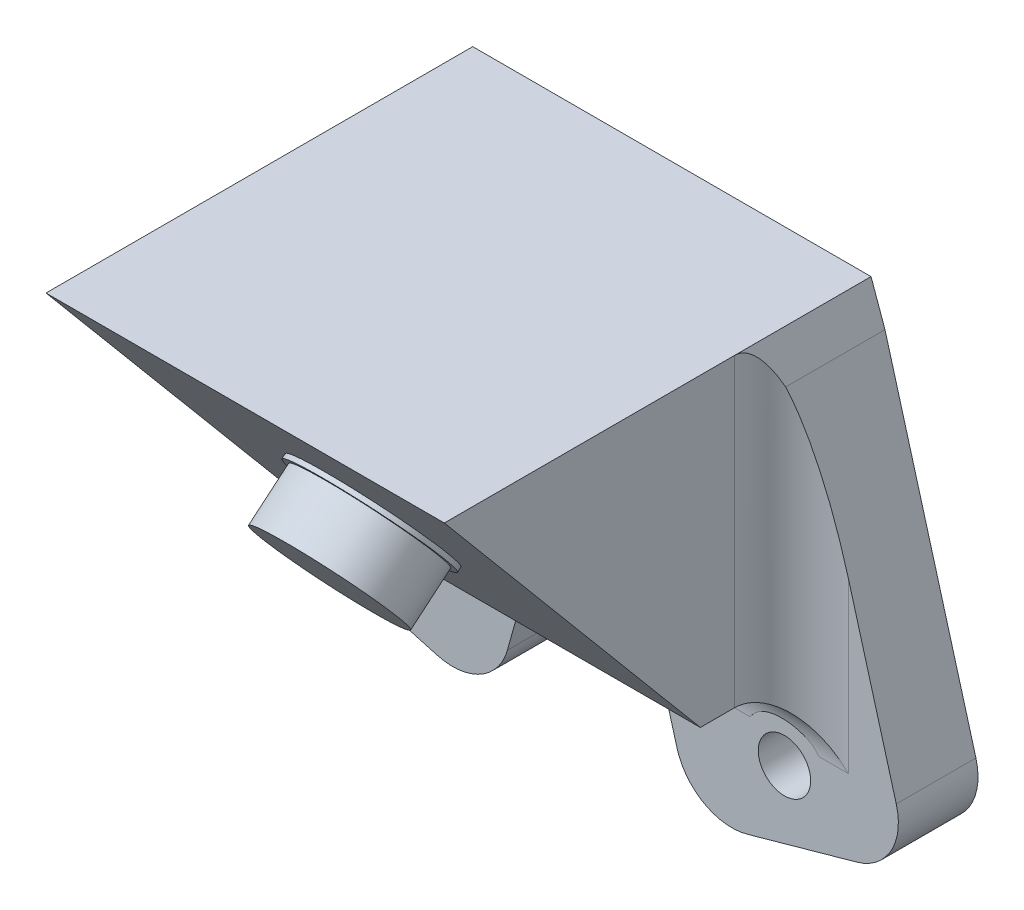
SolidWorks part; units mm, degrees
ref_plane "Ebene vorne" through (0, 0, 0) normal (0, 0, 1) x (1, 0, 0)
ref_plane "Ebene oben" through (0, 0, 0) normal (0, 1, 0) x (1, 0, 0)
ref_plane "Ebene rechts" through (0, 0, 0) normal (1, 0, 0) x (0, 0, -1)
sketch "Skizze1" plane through (0, 0, 0) normal (1, 0, 0) x (0, 0, -1)
  line L0 (0, 0) -> (26.8116, 0)
  line L1 (0, 0) -> (0, 15)
  line L2 (0, 15) -> (26.8116, 37.4976)
  line L3 (26.8116, 37.4976) -> (26.8116, 0)
  dimension "D1" = 40
  dimension "D2" = 15
  dimension "D3" = 35
extrude "Aufsatz-Linear austragen1" add sketch "Skizze1" along normal blind 35
sketch "Skizze3" plane through (0, 8.8024, 7.3861) normal (0, 0.766, 0.6428) x (1, 0, 0)
  line L0 (0, 44.6418) -> (35, 9.6418) construction
  line L1 (17.5, 27.1418) -> (35, 44.6418) construction
  circle A0 centre (17.5, 27.1418) radius 6
  dimension "D1" = 12
extrude "Aufsatz-Linear austragen2" add sketch "Skizze3" along normal blind 5
sketch "Skizze4" plane through (0, 8.8024, 7.3861) normal (0, 0.766, 0.6428) x (1, 0, 0)
  circle A0 centre (17.5, 27.1418) radius 6.5
  dimension "D1" = 13
extrude "Aufsatz-Linear austragen3" add sketch "Skizze4" along normal blind 0.4
ref_plane "Ebene1" through (0, 15, 0) normal (0, -1, 0) x (-1, 0, 0)
sketch "Skizze7" plane through (0, 15, 0) normal (0, -1, 0) x (-1, 0, 0)
  line L1 (-35, 0) -> (0, 26.8116) construction
  line L2 (-17.5, 13.4058) -> (-17.5, 26.8116) construction
  line L3 (-35, 26.8116) -> (0, 26.8116) construction
  line L4 (-17.5, 13.4058) -> (-35, 13.4058) construction
  line L5 (-35, 0) -> (-35, 26.8116) construction
  circle A0 centre (-28.5, 21.8116) radius 2.85
  circle A1 centre (-6.5, 21.8116) radius 2.85
  circle A2 centre (-6.5, 5) radius 2.85
  circle A3 centre (-28.5, 5) radius 2.85
  dimension "D1" = 5.7
  dimension "D2" = 11
  dimension "D3" = 5
extrude "Schnitt-Linear austragen1" [suppressed] cut sketch "Skizze7" against normal through all
hole_wizard "Ø3.4 (3.4) Durchmesser Bohrung1" [suppressed] positions "3D-Skizze3" profile "Skizze8" hole size "Ø3.4" standard "DIN"
sketch3d "3D-Skizze3" [suppressed]
  line L0 (6.5, 35.6935, -21.8116) -> (6.5, 15, -21.8116) construction
  line L1 (6.5, 21.5869, -5) -> (6.5, 15, -5) construction
  line L2 (28.5, 21.5869, -5) -> (28.5, 15, -5) construction
  line L3 (28.5, 35.6935, -21.8116) -> (28.5, 15, -21.8116) construction
  point P0 (6.5, 15, -21.8116)
  point P4 (6.5, 15, -5)
  point P8 (28.5, 15, -5)
  point P12 (28.5, 15, -21.8116)
sketch "Skizze8" plane through (6.5, 15, -21.8116) normal (1, 0, 0) x (0, 0, 1)
  line L0 (0, 0) -> (0, 15)
  line L1 (0, 15) -> (1.7, 15)
  line L2 (1.7, 15) -> (1.7, 0)
  line L5 (1.7, 0) -> (0, 0)
  line L11 (0, -6.35) -> (0, 107.95) construction
  dimension "Bohrerdurchmesser" = 3.4
  dimension "Bohrungstiefe" = 15
move or copy body "Körper-Verschieben/Kopieren1" bodies to move or copy 103 copy no rotation origin (0, 13.6438, -13.4058) rotation axis (1, 0, 0) rotation angle 90
sketch "Skizze9" plane through (0, 0, -27.0496) normal (0, 0, -1) x (-1, 0, 0)
  line L0 (-13.0068, 0.238) -> (-8.7008, -15.1717)
  line L1 (-35, 0.238) -> (0, 0.238) construction
  line L2 (63.2379, -272.6139) -> (-17.5, 16.3175) construction
  line L3 (-8.7008, -15.1717) -> (10.5613, -9.7891)
  line L4 (82.5, -267.2314) -> (1.7621, 21.7) construction
  line L5 (10.5613, -9.7891) -> (1.2238, 23.6263)
  line L6 (1.2238, 23.6263) -> (0, 27.0496)
  line L7 (0, 27.0496) -> (0, 0.238)
  line L8 (0, 0.238) -> (-13.0068, 0.238)
  line L9 (-17.5, 0.238) -> (-17.5, 7.6415) construction
  line L10 (-45.5613, -9.7891) -> (-36.2238, 23.6263)
  line L11 (-26.2992, -15.1717) -> (-45.5613, -9.7891)
  line L12 (-21.9932, 0.238) -> (-26.2992, -15.1717)
  line L13 (-35, 0.238) -> (-21.9932, 0.238)
  line L14 (-35, 27.0496) -> (-35, 0.238)
  line L15 (-36.2238, 23.6263) -> (-35, 27.0496)
  line L16 (0.9303, -12.4804) -> (-2.4788, -0.2805) construction
  circle A0 centre (-0.6094, -6.9704) radius 2.3
  circle A1 centre (-34.3906, -6.9704) radius 2.3
  dimension "D2" = 4.6
  dimension "D1" = 16
extrude "Aufsatz-Linear austragen4" add sketch "Skizze9" against normal blind 7
fillet "Verrundung1" radius 5 10 edges at (35, 13.6438, -20.0496) (28.4966, 0.238, -20.0496) (6.5034, 0.238, -20.0496) (0, 13.6438, -20.0496) (45.5613, -9.7891, -23.5496) (26.2992, -15.1717, -23.5496) (8.7008, -15.1717, -23.5496) (-10.5613, -9.7891, -23.5496) (21.9932, 0.238, -23.5496) (13.0068, 0.238, -23.5496)
sketch "Skizze11" plane through (0, 0, -20.0496) normal (0, 0, 1) x (1, 0, 0)
  circle A0 centre (0.6094, -6.9704) radius 3.75
  circle A1 centre (34.3906, -6.9704) radius 3.75
  dimension "D1" = 7.5
extrude "Schnitt-Linear austragen2" cut sketch "Skizze11" along normal blind 10
sketch "Skizze12" plane through (0, 0, -27.0496) normal (0, 0, -1) x (-1, 0, 0)
  circle A0 centre (-17.5, 21.8738) radius 1.425
  dimension "D1" = 2.85
extrude "Schnitt-Linear austragen3" cut sketch "Skizze12" against normal blind 9
